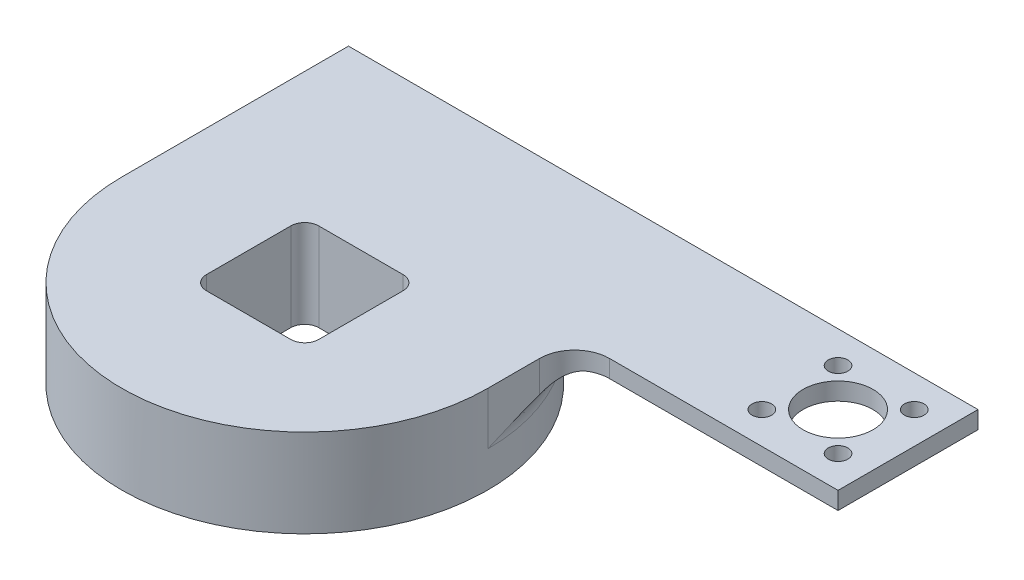
SolidWorks part; units mm, degrees
material "6061-T6 (SS)"
ref_plane "Front Plane" through (0, 0, 0) normal (0, 0, 1) x (1, 0, 0)
ref_plane "Top Plane" through (0, 0, 0) normal (0, 1, 0) x (1, 0, 0)
ref_plane "Right Plane" through (0, 0, 0) normal (1, 0, 0) x (0, 0, -1)
sketch "Sketch1" plane through (0, 0, 0) normal (0, 1, 0) x (1, 0, 0)
  line L0 (-1.1049, 0) -> (-33.2105, 0) construction
  line L1 (-1.1049, 0) -> (33.2105, 0) construction
  circle A0 centre (0, 0) radius 33.2105
  dimension "D1" = 66.421
extrude "Boss-Extrude1" add sketch "Sketch1" along normal blind 16.002
sketch "Sketch2" plane through (0, 16.002, 0) normal (0, 1, 0) x (1, 0, 0)
  line L0 (0, 0) -> (-33.2105, 0) construction
  line L1 (0, 0) -> (33.2105, 0) construction
  line L2 (-33.2105, 0) -> (-33.2105, 41.148)
  line L3 (-33.2105, 41.148) -> (81.026, 41.148)
  line L4 (81.026, 41.148) -> (81.026, 15.748)
  line L5 (33.2105, 0) -> (33.2105, 15.748)
  line L6 (33.2105, 15.748) -> (81.026, 15.748)
  circle A0 centre (0, 0) radius 33.2105 construction
  circle A2 centre (0, 0) radius 33.2105
  arc A3 (-33.2105, 0) -> (33.2105, 0) centre (0, 0) ccw
  dimension "D1" = 0
extrude "Boss-Extrude2" add sketch "Sketch2" against normal blind 3.175
fillet "Fillet1" radius 6.35 1 edges at (0, 12.827, -33.2105)
fillet "Fillet2" radius 6.35 1 edges at (33.2105, 14.0878, -15.748)
sketch "Sketch4" plane through (0, 16.002, 0) normal (0, 1, 0) x (1, 0, 0)
  line L0 (81.026, 41.148) -> (58.166, 41.148) construction
  line L1 (81.026, 41.148) -> (-33.2105, 41.148) construction
  line L2 (58.166, 41.148) -> (58.166, 28.448) construction
  line L3 (58.166, 28.448) -> (78.486, 28.448) construction
  line L4 (68.326, 28.448) -> (75.2408, 35.3628) construction
  line L5 (68.326, 28.448) -> (75.2408, 21.5332) construction
  line L6 (68.326, 28.448) -> (61.4112, 21.5332) construction
  line L7 (68.326, 28.448) -> (61.4112, 35.3628) construction
  circle A0 centre (61.4112, 35.3628) radius 1.778
  circle A1 centre (75.2408, 35.3628) radius 1.778
  circle A2 centre (75.2408, 21.5332) radius 1.778
  circle A3 centre (68.326, 28.448) radius 6.35
  circle A4 centre (61.4112, 21.5332) radius 1.778
extrude "Cut-Extrude2" cut sketch "Sketch4" against normal up to next
sketch "Sketch5" plane through (0, 16.002, 0) normal (0, 1, 0) x (1, 0, 0)
  line L1 (10.1926, 10.1926) -> (-10.1926, 10.1926)
  line L2 (10.1926, 10.1926) -> (10.1926, -10.1926)
  line L3 (10.1926, -10.1926) -> (-10.1926, -10.1926)
  line L4 (-10.1926, 10.1926) -> (-10.1926, -10.1926)
  line L5 (10.1926, 10.1926) -> (-10.1926, -10.1926) construction
  line L6 (10.1926, -10.1926) -> (-10.1926, 10.1926) construction
  point P0 (0, 0)
  dimension "D1" = 28.829
extrude "Cut-Extrude3" cut sketch "Sketch5" against normal up to next
fillet "Fillet3" radius 2.54 1 edges at (-10.1926, 8.001, -10.1926)
fillet "Fillet4" radius 2.54 1 edges at (10.1926, 8.001, -10.1926)
fillet "Fillet5" radius 2.54 1 edges at (10.1926, 8.001, 10.1926)
fillet "Fillet6" radius 2.54 1 edges at (-10.1926, 8.001, 10.1926)
